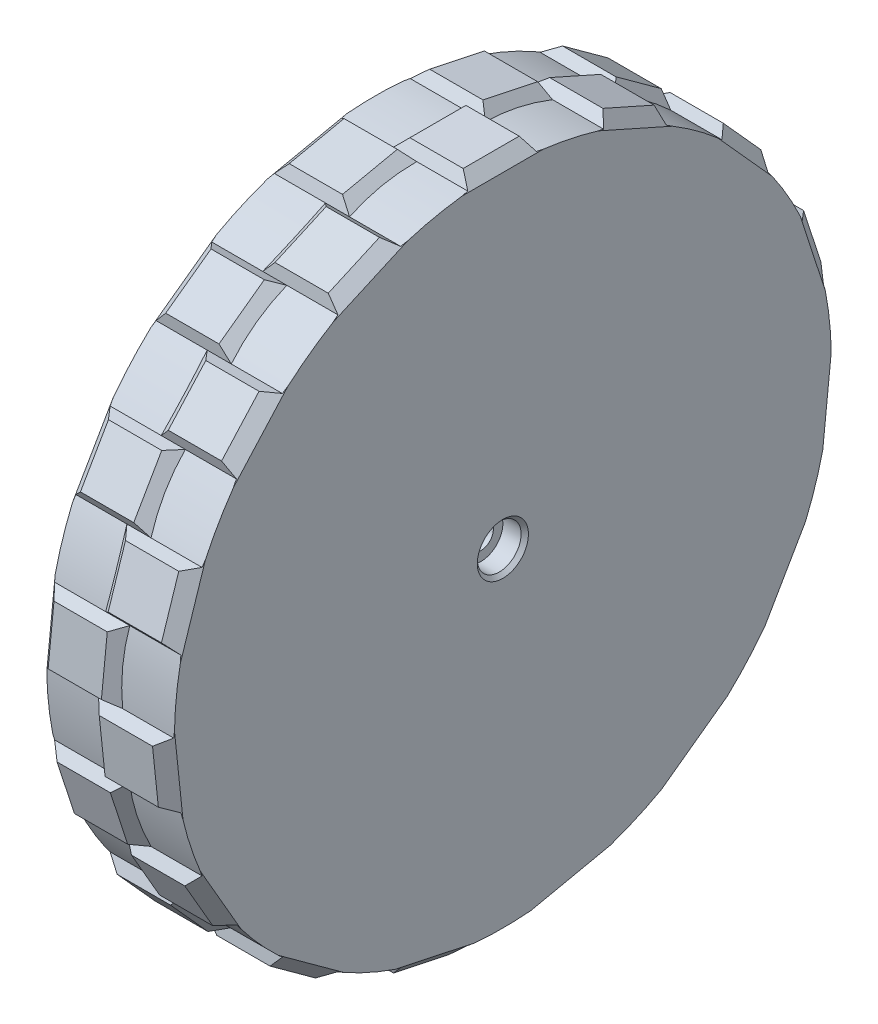
SolidWorks part; units mm, degrees
ref_plane "Front Plane" through (0, 0, 0) normal (0, 0, 1) x (1, 0, 0)
ref_plane "Top Plane" through (0, 0, 0) normal (0, 1, 0) x (1, 0, 0)
ref_plane "Right Plane" through (0, 0, 0) normal (1, 0, 0) x (0, 0, -1)
sketch "Sketch1" plane through (0, 0, 0) normal (1, 0, 0) x (0, 0, -1)
  circle A0 centre (0, 0) radius 45
  dimension "D1" = 90
extrude "Boss-Extrude1" add sketch "Sketch1" along normal blind 17.5
sketch "Sketch2" plane through (17.5, 0, 0) normal (1, 0, 0) x (0, 0, -1)
  line L0 (-4.7038, 44.7535) -> (-3.8378, 46.2535)
  line L1 (-3.8378, 46.2535) -> (3.8378, 46.2535)
  line L2 (3.8378, 46.2535) -> (4.7038, 44.7535)
  line L3 (4.7038, 44.7535) -> (-4.7038, 44.7535)
  line L4 (-4.7038, 44.7535) -> (0, 0) construction
  line L5 (0, 0) -> (4.7038, 44.7535) construction
  circle A0 centre (0, 0) radius 45 construction
  point P4 (0, 44.7535)
  dimension "D1" = 60
  dimension "D2" = 60
  dimension "D4" = 1.5
  dimension "D3" = 12
extrude "Boss-Extrude2" add sketch "Sketch2" against normal blind 10.5
chamfer "Chamfer1" distance 1.6 angle 45 2 edges at (17.5, 46.2535, 0) (7, 46.2535, 0)
pattern_circular "CirPattern1" count 15 over 360 about axis through (17.5, 0, 0) along (1, 0, 0) of "Boss-Extrude2", "Chamfer1"
sketch "Sketch4" plane through (0, 0, 0) normal (-1, 0, 0) x (0, 0, 1)
  line L0 (0, 45) -> (0, 0) construction
  line L1 (0, 0) -> (-9.356, 44.0166) construction
  line L6 (-13.9058, 42.7975) -> (-4.7038, 44.7535)
  line L7 (-4.7038, 44.7535) -> (-5.8627, 46.0406)
  line L8 (-5.8627, 46.0406) -> (-13.3705, 44.4448)
  line L9 (-13.3705, 44.4448) -> (-13.9058, 42.7975)
  line L10 (-13.9058, 42.7975) -> (0, 0) construction
  line L11 (0, 0) -> (-4.7038, 44.7535) construction
  circle A1 centre (0, 0) radius 45 construction
  point P13 (-9.3048, 43.7755)
  dimension "D2" = 60
  dimension "D1" = 12
  dimension "D3" = 60
  dimension "D4" = 12
  dimension "D5" = 1.5
extrude "Boss-Extrude3" add sketch "Sketch4" against normal blind 10.5
chamfer "Chamfer2" distance 1.6 angle 45 2 edges at (10.5, 45.2427, -9.6166) (0, 45.2427, -9.6166)
pattern_circular "CirPattern2" count 15 over 360 about axis through (0, 0, 0) along (1, 0, 0) of "Boss-Extrude3", "Chamfer2"
sketch "Sketch5" plane through (0, 0, 0) normal (-1, 0, 0) x (0, 0, 1)
  line L0 (-1.7593, 2.43) -> (1.7593, 2.43) construction
  line L1 (-1.7993, 2.555) -> (1.7993, 2.555)
  arc A0 (-1.7593, 2.43) -> (1.7593, 2.43) centre (0, 0) ccw construction
  arc A1 (-1.7993, 2.555) -> (1.7993, 2.555) centre (0, 0) ccw
  dimension "D1" = 6
  dimension "D2" = 2.43
  dimension "D3" = 0.125
extrude "Cut-Extrude1" cut sketch "Sketch5" against normal blind 6
chamfer "Chamfer4" distance 0.5 angle 45 2 edges at (0, 2.555, 0) (0, -3.125, 0)
sketch "Sketch6" plane through (17.5, 0, 0) normal (1, 0, 0) x (0, 0, -1)
  circle A0 centre (0, 0) radius 3
  dimension "D1" = 6
extrude "Cut-Extrude2" cut sketch "Sketch6" against normal blind 3
chamfer "Chamfer5" distance 0.5 angle 45 1 edges at (17.5, 0, -3)
sketch "Sketch7" plane through (6, 0, 0) normal (-1, 0, 0) x (0, 0, 1)
  circle A0 centre (0, 0) radius 1.7
  dimension "D1" = 3.4
extrude "Cut-Extrude3" cut sketch "Sketch7" against normal up to next
equation "\"D2@Sketch2\"=\"D1@Sketch2\""
equation "\"D3@Sketch4\"=\"D2@Sketch4\""
equation "\"Num Treads\"= 15"
equation "\"D1@CirPattern1\"=\"Num Treads\""
equation "\"D1@CirPattern2\"=\"Num Treads\""
